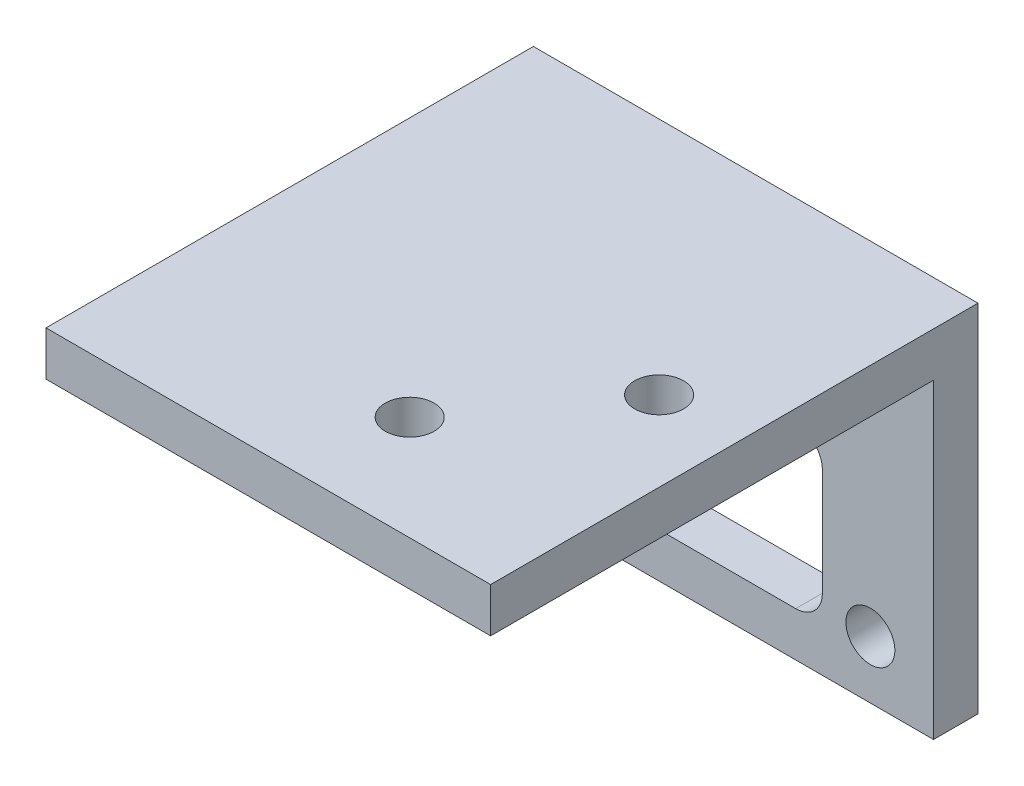
SolidWorks part; units mm, degrees
ref_plane "Front Plane" through (0, 0, 0) normal (0, 0, 1) x (1, 0, 0)
ref_plane "Top Plane" through (0, 0, 0) normal (0, 1, 0) x (1, 0, 0)
ref_plane "Right Plane" through (0, 0, 0) normal (1, 0, 0) x (0, 0, -1)
sketch "Sketch1" plane through (0, 0, 0) normal (0, 0, 1) x (1, 0, 0)
  line L0 (25, 40) -> (25, 0) construction
  line L1 (0, 0) -> (50, 0)
  line L2 (0, 0) -> (0, 40)
  line L3 (0, 40) -> (50, 40)
  line L4 (50, 0) -> (50, 40)
  line L5 (7.1, 6.5) -> (42.9, 6.5) construction
  line L6 (12.5, 23) -> (12.5, 5)
  line L9 (12.5, 23) -> (37.5, 23)
  line L10 (12.5, 5) -> (37.5, 5)
  line L11 (37.5, 23) -> (37.5, 5)
  circle A0 centre (7.1, 6.5) radius 2.75
  circle A1 centre (42.9, 6.5) radius 2.75
  circle A4 centre (15, 29.5) radius 2.75
  circle A6 centre (35, 29.5) radius 2.75
  point P15 (25, 5)
  point P16 (25, 23)
  dimension "D3" = 5.5
  dimension "D5" = 6.5
  dimension "D1" = 50
  dimension "D2" = 40
  dimension "D4" = 35.8
  dimension "D6" = 18
  dimension "D7" = 5
  dimension "D8" = 23
  dimension "D9" = 20
  dimension "D10" = 25
extrude "Boss-Extrude1" add sketch "Sketch1" along normal blind 5
sketch "Sketch2" plane through (0, 0, 5) normal (0, 0, 1) x (1, 0, 0)
  line L0 (0, 40) -> (0, 0) construction
  line L1 (0, 40) -> (50, 40)
  line L2 (0, 40) -> (0, 35)
  line L3 (0, 35) -> (50, 35)
  line L4 (50, 40) -> (50, 35)
  line L5 (50, 40) -> (0, 40) construction
  line L6 (50, 0) -> (50, 40) construction
  dimension "D1" = 5
extrude "Boss-Extrude2" add sketch "Sketch2" along normal blind 49.81
sketch "Sketch3" plane through (0, 35, 0) normal (0, -1, 0) x (1, 0, 0)
  line L0 (0, 54.81) -> (50, 54.81) construction
  line L2 (50, 54.81) -> (50, 5) construction
  circle A0 centre (29.15, 43.06) radius 2.75
  circle A1 centre (41, 26.86) radius 2.75
  dimension "D1" = 5.5
  dimension "D3" = 9
  dimension "D4" = 9
  dimension "D5" = 20.85
  dimension "D2" = 25.2
extrude "Cut-Extrude1" cut sketch "Sketch3" against normal up to next
fillet "Fillet1" radius 3 4 edges at (37.5, 5, 2.5) (37.5, 23, 2.5) (12.5, 23, 2.5) (12.5, 5, 2.5)
